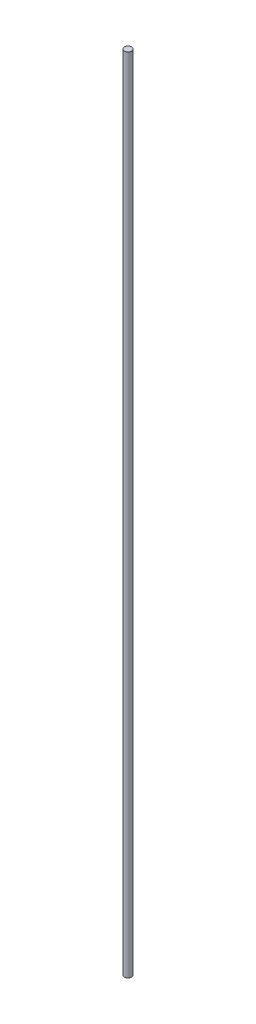
SolidWorks part; units mm, degrees
ref_plane "Спереди" through (0, 0, 0) normal (0, 0, 1) x (1, 0, 0)
ref_plane "Сверху" through (0, 0, 0) normal (0, 1, 0) x (1, 0, 0)
ref_plane "Справа" through (0, 0, 0) normal (1, 0, 0) x (0, 0, -1)
sketch "Эскиз2" plane through (0, 0, 0) normal (0, 0, 1) x (1, 0, 0)
  line L5 (-2.5, 272) -> (0, 272)
  line L6 (-2.5, 272) -> (-2.5, -272)
  line L7 (-2.5, -272) -> (0, -272)
  line L8 (0, 272) -> (0, -272)
  line L9 (-2.5, 272) -> (0, -272) construction
  line L10 (-2.5, -272) -> (0, 272) construction
  point P0 (-1.25, 0)
  point P5 (0, 0)
  dimension "D1" = 2.5
  dimension "D2" = 544
revolve "Повернуть1" add sketch "Эскиз2" angle 360 about L6
equation "\"Ширина груза\"= 420"
equation "\"Глубина груза\"= 490"
equation "\"Высота груза\"= 297"
equation "\"Ширина ячейки\"= \"Ширина груза\" + 10"
equation "\"Глубина ячейки\"= \"Глубина груза\" + 10"
equation "\"Высота ячейки\"= \"Высота груза\" + 10 + 13"
equation "\"Колво ячеек ширина\"= 2"
equation "\"Колво ячеек высота\"= 2"
equation "\"Толщина стенки\" = 6"
equation "\"Крепление дверцы\"= 5 "
equation "\"Ширина рейки\"= \"Толщина шестерни\""
equation "\"Высота рейки\"= 20"
equation "\"Высота пола\"= \"Толщина стенки\" * 2"
equation "\"Колво полозьев\"= 5"
equation "\"Отступ рейки\"= 20"
equation "\"Глубина каретки\"= \"Глубина ячейки\" + 30 + \"Мотор Y высота корпуса\" + 20"
equation "\"Длинна рейки\" = (\"Ширина ячейки\" + \"Толщина стенки\" + \"Крепление дверцы\") * \"Колво ячеек ширина\" + \"Ширина ячейки выгрузки\" * \"Колво выгрузки\" + \"Толщина стенки\" + \"Отступ крепления мотора фиксации\" * 2 - \"Крепление дверцы\" * \"Колво ячеек ширина\""
equation "\"Отступ шпильки\"= 26"
equation "\"Диаметр шпильки\"= 5"
equation "\"Длинна шпильки\"= ( \"Высота ячейки\" + \"Толщина стенки\" + \"Высота пола\" ) * \"Колво ячеек высота\" + ( \"Толщина стенки\" + \"Отступ рейки\" ) * 2 "
equation "\"D1@Эскиз2\"= \"Диаметр шпильки\" / 2"
equation "\"D2@Эскиз2\" = \"Глубина каретки\" - \"Мотор Y высота корпуса\" - \"Толщина стенки\""
equation "\"Ширина пластины\"= 50  "
equation "\"Высота зона выгрузки\"= \"Высота ячейки\" * 2 + \"Толщина стенки\" * 2"
equation "\"Колво выгрузки\"= 1"
equation "\"Отступ крепления мотора фиксации\" = (\"Ширина пластины\" + 20 - \"Толщина стенки\") / 2"
equation "\"Мотор X ширина корпуса\"= 42.3"
equation "\"Мотор X высота корпуса\"= 42.3"
equation "\"Мотор X длина корпуса\"= 40"
equation "\"Мотор X вылет вала\"= 19.8"
equation "\"Мотор Y ширина корпуса\"= 42.3"
equation "\"Мотор Y высота корпуса\"= 42.3"
equation "\"Мотор Y длина корпуса\"= 48"
equation "\"Мотор Y вылет вала\"= 30"
equation "\"Мотор Z ширина корпуса\"= 42"
equation "\"Мотор Z высота корпуса\"= 42"
equation "\"Мотор Z длина корпуса\"= 40"
equation "\"Мотор Z вылет вала\"= 23"
equation "\"Мотор диаметр вала ПРЕДВ\"= 5"
equation "\"Мотор шаг крепления ПРЕДВ\"= 31"
equation "\"Мотор диаметр отверстий ПРЕДВ\"= 3"
equation "\"Мотор глубина отверстий ПРЕДВ\"= 4.5"
equation "\"Мотор диаметр буртика ПРЕДВ\"= 22"
equation "\"Мотор высота буртика ПРЕДВ\"= 2"
equation "\"Мотор диаметр шкива ПРЕДВ\"= 16"
equation "\"Мотор длина шкива ПРЕДВ\"= 12"
equation "\"Мотор отступ шкива ПРЕДВ\"= 5"
equation "\"Мотор X шаг градусов\"= 1.8"
equation "\"Мотор X ток А\"= 1.5"
equation "\"Мотор X сопротивление Ом\"= 1.3"
equation "\"Мотор X индуктивность мГн\"= 2"
equation "\"Мотор Y шаг градусов\"= 1.8"
equation "\"Мотор Y ток А\"= 2.2"
equation "\"Мотор Y сопротивление Ом\"= 0.9"
equation "\"Мотор Y индуктивность мГн\"= 2"
equation "\"Мотор Z шаг градусов\"= 1.8"
equation "\"Мотор Z ток А\"= 1"
equation "\"Мотор Z сопротивление Ом\"= 4"
equation "\"Мотор Z индуктивность мГн\"= 8"
equation "\"Мотор Y диаметр ротора\"= 25.78"
equation "\"Ширина ячейки выгрузки\"= \"Ширина ячейки\" + \"Толщина стенки\" + \"Отступ крепления мотора фиксации\"*2"
